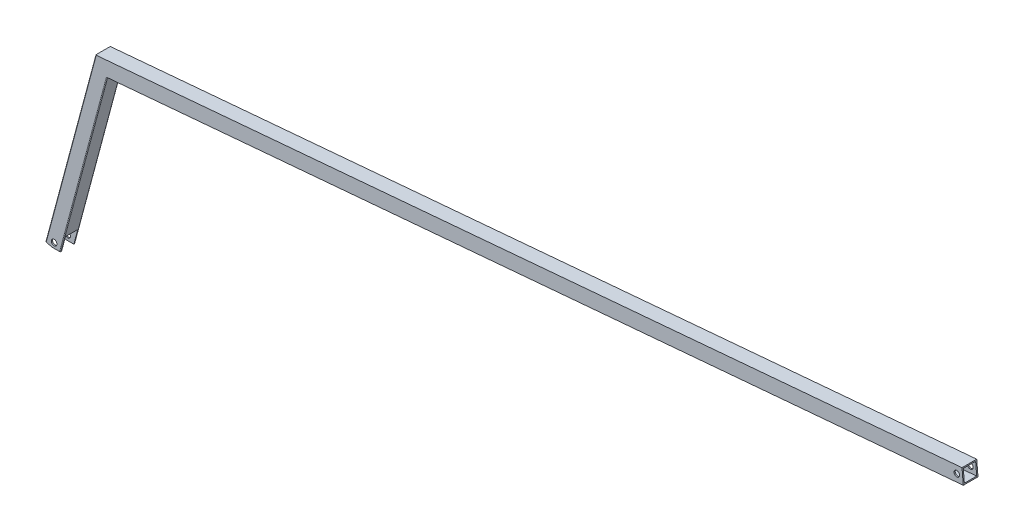
SolidWorks part; units mm, degrees
ref_plane "Front Plane" through (0, 0, 0) normal (0, 0, 1) x (1, 0, 0)
ref_plane "Top Plane" through (0, 0, 0) normal (0, 1, 0) x (1, 0, 0)
ref_plane "Right Plane" through (0, 0, 0) normal (1, 0, 0) x (0, 0, -1)
sketch "Sketch1" plane through (0, -98.298, 0) normal (0, 0, -1) x (-1, 0, 0)
  line L0 (32.8955, -12.2438) -> (1529.2366, -143.1567)
  line L1 (1529.2366, -143.1567) -> (1615.5675, -465.3482)
  line L2 (1615.5675, -465.3482) -> (1591.033, -471.9222)
  line L3 (1591.033, -471.9222) -> (1509.3052, -166.91)
  line L4 (1509.3052, -166.91) -> (30.6818, -37.5472)
  line L5 (30.6818, -37.5472) -> (32.8955, -12.2438)
  line L6 (22.8132, -24.1102) -> (105.6727, -31.3595) construction
  line L7 (804.8625, -417.5248) -> (1577.975, -417.5248) construction
  line L8 (1577.975, -284.1748) -> (1577.975, -417.5248) construction
  line L9 (1595.8038, -440.6582) -> (-11345.1484, 47855.6331) construction
  circle A0 centre (41.91, -25.781) radius 4.826
  circle A1 centre (41.91, -25.781) radius 4.8641 construction
  circle A2 centre (1600.835, -459.4348) radius 4.826
  circle A3 centre (1600.835, -459.4348) radius 3.175 construction
  point P9 (31.7887, -24.8955)
  dimension "D3" = 9.652
  dimension "D1" = 25.4
  dimension "D2" = 25.4
  dimension "D4" = 10.16
  dimension "D5" = 5
  dimension "D6" = 15
  dimension "D7" = 9.525
extrude "Boss-Extrude1" add sketch "Sketch1" along normal mid plane 25.4 contours A2 | A0 | L3 L4 L5 L0 L1 L2 region at (-41.91, -124.079, 0) region at (-1600.835, -557.7328, 0)
shell "Shell1" thickness 2.0574 removed face at (-31.7887, -123.1935, 0) removed face at (-1605.661, -557.7328, -12.7) removed face at (-1603.3003, -566.9332, 0) removed face at (-46.736, -124.079, -12.7)
fillet "Fillet1" radius 1.27 8 edges at (-1570.6012, -403.7787, -10.6426) (-1570.6012, -403.7787, 10.6426) (-1551.97, -416.4858, -10.6426) (-1551.97, -416.4858, 10.6426) (-1550.1691, -417.7141, 12.7) (-1572.402, -402.5505, 12.7) (-1572.402, -402.5505, -12.7) (-1550.1691, -417.7141, -12.7)
sketch "Sketch2" plane through (0, 0, -12.7) normal (0, 0, -1) x (-1, 0, 0)
  line L0 (1604.4588, -566.6228) -> (1590.0691, -566.6228)
  line L1 (1614.3408, -563.9749) -> (1592.2597, -569.8915) construction
  line L2 (-57.15, -566.6228) -> (1616.075, -566.6228) construction
  line L3 (1591.033, -570.2202) -> (1509.3052, -265.208) construction
  line L4 (1590.0691, -566.6228) -> (1591.033, -570.2202)
  line L5 (1591.033, -570.2202) -> (1604.4588, -566.6228)
extrude "Cut-Extrude1" cut sketch "Sketch2" against normal through all
sketch "Sketch3" plane through (0, 0, 0) normal (1, 0, 0) x (0, 0, -1)
  line L1 (10.6426, -566.6228) -> (-10.6426, -566.6228)
  line L2 (10.6426, -566.6228) -> (10.6426, -541.2228)
  line L3 (10.6426, -541.2228) -> (-10.6426, -541.2228)
  line L4 (-10.6426, -566.6228) -> (-10.6426, -541.2228)
  line L5 (-4.6736, -546.3028) -> (4.6736, -546.3028) construction
  line L6 (0, -1000) -> (0, 49000) construction
  line L7 (762, -566.6228) -> (-1635.125, -566.6228) construction
  line L10 (-10.6426, -562.5588) -> (-10.6426, -552.9068) construction
  dimension "D1" = 5.08
extrude "Cut-Extrude2" cut sketch "Sketch3" against normal through all
fillet "Fillet2" radius 1.27 4 edges at (-1607.8368, -541.2228, -10.6426) (-1584.9855, -541.2228, -10.6426) (-1607.8368, -541.2228, 10.6426) (-1584.9855, -541.2228, 10.6426)
